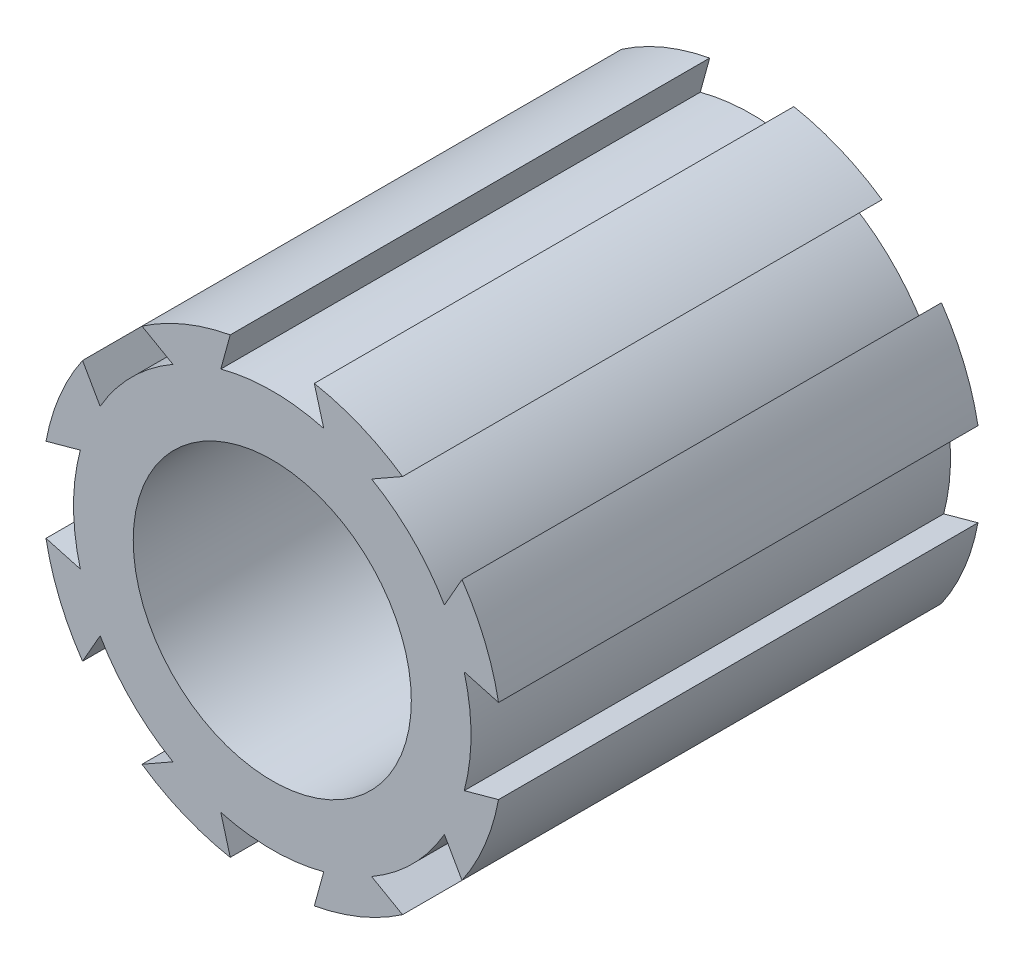
SolidWorks part; units mm, degrees
material "Alumine"
ref_plane "Plan de face" through (0, 0, 0) normal (0, 0, 1) x (1, 0, 0)
ref_plane "Plan de dessus" through (0, 0, 0) normal (0, 1, 0) x (1, 0, 0)
ref_plane "Plan de droite" through (0, 0, 0) normal (1, 0, 0) x (0, 0, -1)
sketch "Esquisse5" plane through (0, 0, 0) normal (0, 0, 1) x (1, 0, 0)
  circle A0 centre (0, 0) radius 14.5
  circle A1 centre (0, 0) radius 24
extrude "Boss.-Extru.2" add sketch "Esquisse5" along normal blind 50
sketch "Esquisse6" plane through (0, 0, 0) normal (0, 0, 1) x (1, 0, 0)
  line L0 (0, 0) -> (0, 24)
  line L1 (-4.3841, 23.5962) -> (-5.3678, 20.0177)
  line L2 (4.3841, 23.5962) -> (5.3678, 20.0177)
  line L3 (19.785, 13.585) -> (17.9502, 10.3591)
  line L4 (13.585, 19.785) -> (10.3591, 17.9502)
  line L5 (23.5962, -4.3841) -> (20.0177, -5.3678)
  line L6 (23.5962, 4.3841) -> (20.0177, 5.3678)
  line L7 (13.585, -19.785) -> (10.3591, -17.9502)
  line L8 (19.785, -13.585) -> (17.9502, -10.3591)
  line L9 (-4.3841, -23.5962) -> (-5.3678, -20.0177)
  line L10 (4.3841, -23.5962) -> (5.3678, -20.0177)
  line L11 (-19.785, -13.585) -> (-17.9502, -10.3591)
  line L12 (-13.585, -19.785) -> (-10.3591, -17.9502)
  line L13 (-23.5962, 4.3841) -> (-20.0177, 5.3678)
  line L14 (-23.5962, -4.3841) -> (-20.0177, -5.3678)
  line L15 (-13.585, 19.785) -> (-10.3591, 17.9502)
  line L16 (-19.785, 13.585) -> (-17.9502, 10.3591)
  circle A0 centre (0, 0) radius 24 construction
  arc A1 (-5.3678, 20.0177) -> (5.3678, 20.0177) centre (0, 0) cw
  arc A2 (-4.3841, 23.5962) -> (4.3841, 23.5962) centre (0, 0) cw
  arc A3 (13.585, 19.785) -> (19.785, 13.585) centre (0, 0) cw
  arc A4 (10.3591, 17.9502) -> (17.9502, 10.3591) centre (0, 0) cw
  arc A5 (23.5962, 4.3841) -> (23.5962, -4.3841) centre (0, 0) cw
  arc A6 (20.0177, 5.3678) -> (20.0177, -5.3678) centre (0, 0) cw
  arc A7 (19.785, -13.585) -> (13.585, -19.785) centre (0, 0) cw
  arc A8 (17.9502, -10.3591) -> (10.3591, -17.9502) centre (0, 0) cw
  arc A9 (4.3841, -23.5962) -> (-4.3841, -23.5962) centre (0, 0) cw
  arc A10 (5.3678, -20.0177) -> (-5.3678, -20.0177) centre (0, 0) cw
  arc A11 (-13.585, -19.785) -> (-19.785, -13.585) centre (0, 0) cw
  arc A12 (-10.3591, -17.9502) -> (-17.9502, -10.3591) centre (0, 0) cw
  arc A13 (-23.5962, -4.3841) -> (-23.5962, 4.3841) centre (0, 0) cw
  arc A14 (-20.0177, -5.3678) -> (-20.0177, 5.3678) centre (0, 0) cw
  arc A15 (-19.785, 13.585) -> (-13.585, 19.785) centre (0, 0) cw
  arc A16 (-17.9502, 10.3591) -> (-10.3591, 17.9502) centre (0, 0) cw
  point P40 (0, 0)
  dimension "D1" = 8
extrude "Enlèv. mat.-Extru.4" cut sketch "Esquisse6" along normal through all and the other way blind 16 contours A14 L13 A13 L14 | A16 L15 A15 L16 | A1 L2 A2 L1 | A4 L3 A3 L4 | A6 L5 A5 L6 | A8 L7 A7 L8 | A10 L9 A9 L10 | A12 L11 A11 L12
